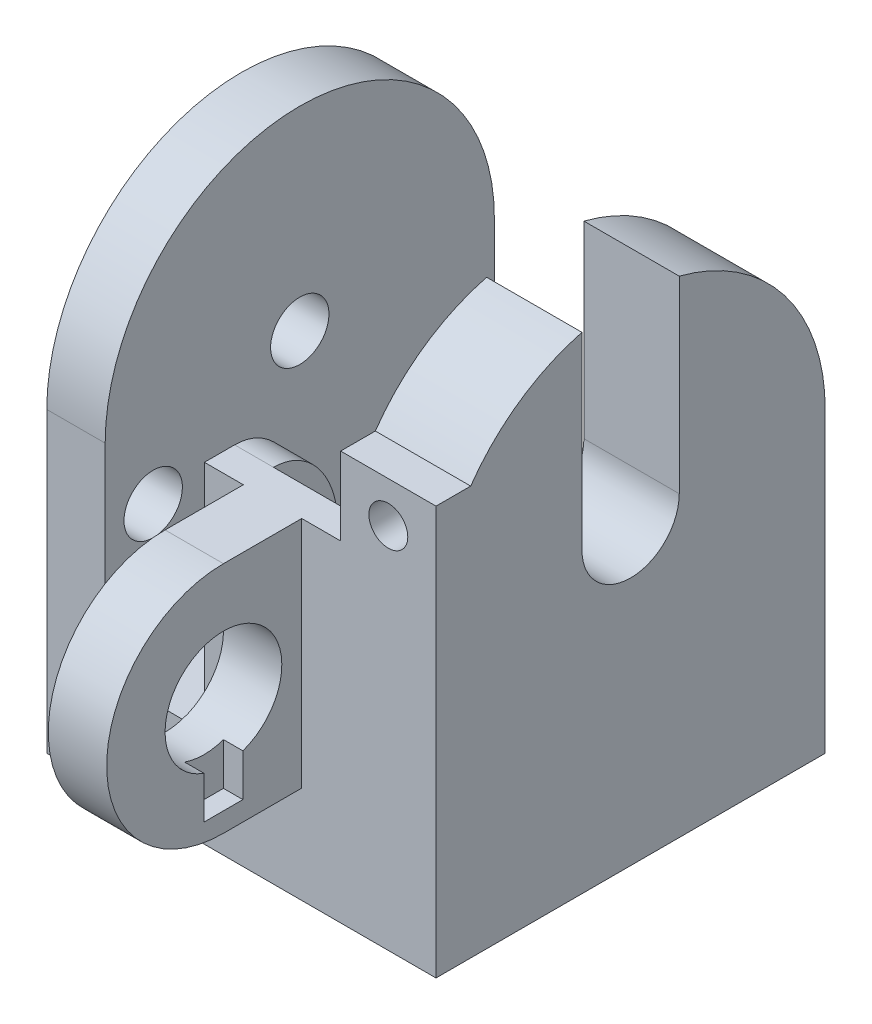
SolidWorks part; units mm, degrees
ref_plane "Front Plane" through (0, 0, 0) normal (0, 0, 1) x (1, 0, 0)
ref_plane "Top Plane" through (0, 0, 0) normal (0, 1, 0) x (1, 0, 0)
ref_plane "Right Plane" through (0, 0, 0) normal (1, 0, 0) x (0, 0, -1)
sketch "Sketch1" plane through (0, 0, 0) normal (1, 0, 0) x (0, 0, -1)
  arc A0 (9.7654, 20.1165) -> (-9.7654, 20.1165) centre (0, 22.2701) ccw
  arc A1 (-7.8874, -56.3924) -> (7.8874, -56.3924) centre (0, -57.7299) ccw
  arc A2 (-7.8874, -56.3924) -> (-9.7654, 20.1165) centre (-205.0724, -22.9549) ccw
  circle A3 centre (0, 22.2701) radius 1.5
  arc A4 (9.7654, 20.1165) -> (7.8874, -56.3924) centre (205.0724, -22.9549) ccw
  circle A5 centre (0, -57.7299) radius 2.5
extrude "Boss-Extrude1" add sketch "Sketch1" along normal blind 20
sketch "Sketch2" plane through (0, 0, 0) normal (0, 0, 1) x (1, 0, 0)
  line L1 (0, -65.7299) -> (8.1, -65.7299)
  line L2 (0, -65.7299) -> (0, -45.7299)
  line L3 (0, -45.7299) -> (8.1, -45.7299)
  line L4 (8.1, -65.7299) -> (8.1, -45.7299)
  line L5 (20, -65.7299) -> (14.9, -65.7299)
  line L6 (20, -65.7299) -> (20, -45.7299)
  line L7 (20, -45.7299) -> (14.9, -45.7299)
  line L8 (14.9, -65.7299) -> (14.9, -45.7299)
  line L11 (3, 32.2701) -> (8.1, 32.2701)
  line L12 (3, 32.2701) -> (3, 12.2701)
  line L13 (3, 12.2701) -> (8.1, 12.2701)
  line L14 (8.1, 32.2701) -> (8.1, 12.2701)
extrude "Cut-Extrude1" cut sketch "Sketch2" against normal blind 20 and the other way blind 20
sketch "Sketch3" plane through (8.1, 0, 0) normal (-1, 0, 0) x (0, 0, 1)
  line L0 (8.5, 22.2701) -> (8.5, 40.9095)
  line L1 (8.5, 40.9095) -> (-17.5287, 40.9095)
  line L2 (-17.5287, 40.9095) -> (-17.5287, 13.7701)
  line L3 (0, 13.7701) -> (-17.5287, 13.7701)
  arc A0 (0, 13.7701) -> (8.5, 22.2701) centre (0, 22.2701) ccw
extrude "Cut-Extrude2" cut sketch "Sketch3" against normal blind 9
sketch "Sketch4" plane through (8.1, 0, 0) normal (-1, 0, 0) x (0, 0, 1)
  line L0 (8.5, 27.5379) -> (8.2838, 12.7416)
  line L1 (8.2838, 12.7416) -> (10.2838, 12.7416)
  line L2 (10.2838, 12.7416) -> (10.2838, 27.5379)
  line L3 (10.2838, 27.5379) -> (8.5, 27.5379)
  arc A0 (9.7654, 20.1165) -> (6.3734, -45.7299) centre (205.0724, -22.9549) ccw construction
extrude "Boss-Extrude2" add sketch "Sketch4" against normal through all
sketch "Sketch5" plane through (8.1, 0, 0) normal (-1, 0, 0) x (0, 0, 1)
  line L4 (8.1452, 11.9686) -> (8.4478, 23.9686)
  line L6 (14.0224, 23.9686) -> (9.8547, 23.9686)
  line L8 (8.1452, 11.9686) -> (14.0224, 11.9686)
  line L9 (8.5, 27.5379) -> (8.4045, 20.9993) construction
  line L10 (8.4478, 23.9686) -> (9.8547, 23.9686)
  circle A2 centre (14.0224, 17.9686) radius 3
  arc A5 (14.0224, 11.9686) -> (14.0224, 23.9686) centre (14.0224, 17.9686) ccw
  arc A6 (9.7654, 20.1165) -> (-9.7654, 20.1165) centre (0, 22.2701) ccw construction
  arc A7 (9.7654, 20.1165) -> (6.3734, -45.7299) centre (205.0724, -22.9549) ccw construction
extrude "Boss-Extrude3" add sketch "Sketch5" against normal blind 5
sketch "Sketch12" plane through (13.1, 0, 0) normal (1, 0, 0) x (0, 0, -1)
  line L3 (-15.0224, 13.9686) -> (-15.0224, 12.9686)
  line L4 (-14.0224, 15.1402) -> (-15.0224, 15.1402)
  line L5 (-15.0224, 13.9686) -> (-15.0224, 15.1402)
  line L7 (-15.0224, 12.9686) -> (-13.0224, 12.9686)
  line L8 (-14.0224, 15.1402) -> (-13.0224, 15.1402)
  line L9 (-13.0224, 13.9686) -> (-13.0224, 15.1402)
  line L10 (-13.0224, 13.9686) -> (-13.0224, 12.9686)
  circle A0 centre (-14.0224, 17.9686) radius 3 construction
extrude "Cut-Extrude6" cut sketch "Sketch12" against normal blind 1
sketch "Sketch13" plane through (17.1, 0, 0) normal (-1, 0, 0) x (0, 0, 1)
  circle A0 centre (0, 22.2701) radius 2.5
extrude "Cut-Extrude7" cut sketch "Sketch13" against normal blind 4
sketch "Sketch15" plane through (0, 0, 0) normal (-1, 0, 0) x (0, 0, 1)
  line L0 (10, 22.2701) -> (10, 11.9686)
  line L1 (8.1452, 11.9686) -> (14.0224, 11.9686) construction
  line L2 (10, 11.9686) -> (8.1452, 11.9686)
  line L3 (10, 22.2701) -> (7.5957, 11.9686)
  line L4 (7.5957, 11.9686) -> (8.1452, 11.9686)
  arc A0 (9.7654, 20.1165) -> (-9.7654, 20.1165) centre (0, 22.2701) ccw construction
extrude "Boss-Extrude4" add sketch "Sketch15" against normal blind 3
sketch "Sketch16" plane through (20, 0, 0) normal (1, 0, 0) x (0, 0, -1)
  line L0 (-10.2838, 23.9686) -> (-9.8547, 23.9686)
  line L1 (-10.2838, 23.9686) -> (-10.2838, 27.5379)
  line L2 (-10.2838, 27.5379) -> (-8.5, 27.5379) construction
  line L3 (-10.2838, 12.7416) -> (-10.2838, 27.5379) construction
  line L4 (-10.2838, 27.5379) -> (-8.5, 27.5379)
  arc A0 (-8.5, 27.5379) -> (-9.8547, 23.9686) centre (0, 22.2701) ccw
extrude "Cut-Extrude9" cut sketch "Sketch16" against normal blind 3
sketch "Sketch17" plane through (0, 0, 10.2838) normal (0, 0, 1) x (1, 0, 0)
  line L1 (17.1, 27.5379) -> (8.1, 27.5379)
  line L2 (17.1, 27.5379) -> (17.1, 23.9686)
  line L3 (17.1, 23.9686) -> (8.1, 23.9686)
  line L4 (8.1, 27.5379) -> (8.1, 23.9686)
extrude "Cut-Extrude11" cut sketch "Sketch17" against normal blind 3
sketch "Sketch18" plane through (13.1, 0, 0) normal (1, 0, 0) x (0, 0, -1)
  line L1 (-10.2838, 12.7416) -> (-4.5128, 12.7416)
  line L2 (-10.2838, 12.7416) -> (-10.2838, 11.9686)
  line L3 (-10.2838, 11.9686) -> (-4.5128, 11.9686)
  line L4 (-4.5128, 12.7416) -> (-4.5128, 11.9686)
extrude "Boss-Extrude5" add sketch "Sketch18" along normal through all and the other way blind 1
sketch "Sketch19" plane through (0, 12.2701, 0) normal (0, 1, 0) x (1, 0, 0)
  line L1 (8.1, -8.1989) -> (3, -8.1989)
  line L2 (8.1, -8.1989) -> (8.1, 8.1989)
  line L3 (8.1, 8.1989) -> (3, 8.1989)
  line L4 (3, -8.1989) -> (3, 8.1989)
extrude "Cut-Extrude12" cut sketch "Sketch19" against normal up to surface (0.3015 mm away) up to face at (1.5, 11.9686, 9.0726)
sketch "Sketch20" plane through (17.1, 0, 0) normal (-1, 0, 0) x (0, 0, 1)
  line L1 (2.5, 22.2701) -> (-2.5, 22.2701)
  line L2 (2.5, 22.2701) -> (2.5, 34.6894)
  line L3 (2.5, 34.6894) -> (-2.5, 34.6894)
  line L4 (-2.5, 22.2701) -> (-2.5, 34.6894)
  circle A0 centre (0, 22.2701) radius 2.5 construction
extrude "Cut-Extrude13" cut sketch "Sketch20" against normal blind 10
sketch "Sketch21" plane through (17.1, 0, 0) normal (-1, 0, 0) x (0, 0, 1)
  line L1 (-8.4732, 13.7701) -> (0.2785, 12.274)
  line L3 (2.5, 22.2701) -> (2.5, 31.9526)
  line L5 (-2.5, 22.2701) -> (-2.5, 31.9526)
  arc A0 (0.2785, 12.274) -> (2.5, 31.9526) centre (0, 22.2701) ccw
  arc A1 (-2.5, 22.2701) -> (2.5, 22.2701) centre (0, 22.2701) ccw
  arc A2 (-2.5, 31.9526) -> (-9.7654, 20.1165) centre (0, 22.2701) ccw
  arc A7 (-8.4732, 13.7701) -> (-9.7654, 20.1165) centre (-205.0724, -22.9549) ccw
extrude "Boss-Extrude6" add sketch "Sketch21" along normal blind 2
sketch "Sketch23" plane through (0, 0, 10.2838) normal (0, 0, 1) x (1, 0, 0)
  line L1 (15.1, 23.9686) -> (20, 23.9686)
  line L2 (15.1, 23.9686) -> (15.1, 27.9686)
  line L3 (15.1, 27.9686) -> (20, 27.9686)
  line L4 (20, 23.9686) -> (20, 27.9686)
extrude "Boss-Extrude7" add sketch "Sketch23" against normal blind 4
sketch "Sketch22" plane through (0, 0, 10.2838) normal (0, 0, 1) x (1, 0, 0)
  circle A0 centre (17.55, 25.8701) radius 1
extrude "Cut-Extrude15" cut sketch "Sketch22" against normal blind 8
sketch "Sketch24" plane through (8.1, 0, 0) normal (-1, 0, 0) x (0, 0, 1)
  line L0 (5.1478, 19.7374) -> (5.1478, 15.5063)
  line L2 (8.4478, 23.9686) -> (8.4478, 15.5063)
  line L3 (8.4478, 15.5063) -> (5.1478, 15.5063)
  arc A0 (0, 13.7701) -> (8.3673, 20.7738) centre (0, 22.2701) ccw construction
  ellipse E0 centre (8.4478, 19.7374) end of major axis (8.4478, 15.5063) minor radius 3.3 (8.4478, 23.9686) -> (5.1478, 19.7374) ccw
extrude "Boss-Extrude8" add sketch "Sketch24" against normal blind 2
sketch "Sketch14" plane through (0, 0, 0) normal (-1, 0, 0) x (0, 0, 1)
  circle A3 centre (7.5326, 18.3318) radius 1.5
extrude "Cut-Extrude8" cut sketch "Sketch14" against normal up to surface (10.1 mm away) up to face at (10.1, 20.14, 6.7306)
sketch "Sketch25" plane through (8.1, 0, 0) normal (-1, 0, 0) x (0, 0, 1)
  line L0 (12, -45.7299) -> (8.3462, -36.9607)
  line L1 (-12, -45.7299) -> (-12, -57.7299)
  line L2 (12, -45.7299) -> (12, -57.7299)
  line L3 (-12, -45.7299) -> (-8.3462, -36.9607)
  line L5 (2.5, -53.2274) -> (2.5, -45.7299)
  line L7 (-2.5, -53.2274) -> (-2.5, -45.7299)
  arc A0 (-2.5, -53.2274) -> (2.5, -53.2274) centre (0, -57.7299) ccw
  arc A1 (-12, -57.7299) -> (12, -57.7299) centre (0, -57.7299) ccw
  arc A2 (2.5, -45.7299) -> (8.3462, -36.9607) centre (0, -37.7299) ccw
  arc A4 (-8.3462, -36.9607) -> (-2.5, -45.7299) centre (0, -37.7299) ccw
extrude "Cut-Extrude17" cut sketch "Sketch25" against normal blind 2 and the other way up to surface (8.1 mm away) other way up to face at (0, 18.3318, 9.0326)
sketch "Sketch29" plane through (20, 0, 0) normal (1, 0, 0) x (0, 0, -1)
  line L1 (8, -37.7299) -> (8.1403, -37.7299)
  line L2 (-15.7549, -37.7299) -> (-8, -37.7299)
  line L3 (-15.7549, -37.7299) -> (-15.7549, -45.9375)
  line L4 (-15.7549, -45.9375) -> (8.1403, -45.9375)
  line L5 (8.1403, -37.7299) -> (8.1403, -45.9375)
  arc A0 (-8, -37.7299) -> (8, -37.7299) centre (0, -37.7299) ccw
extrude "Cut-Extrude20" cut sketch "Sketch29" against normal up to surface (5.1 mm away) up to face at (14.9, -57.7299, -2.5)
sketch "Sketch31" plane through (0, 0, 0) normal (-1, 0, 0) x (0, 0, 1)
  line L1 (10, 11.9686) -> (-10, 11.9686)
  line L2 (10, 11.9686) -> (10, 6.9686)
  line L3 (10, 6.9686) -> (-7.3236, 6.9686)
  line L6 (-10, 11.9686) -> (-10, 6.9686)
  line L7 (-10, 6.9686) -> (-7.3236, 6.9686)
  arc A0 (-6.1254, -43.4508) -> (-9.7654, 20.1165) centre (-205.0724, -22.9549) ccw construction
extrude "Boss-Extrude9" add sketch "Sketch31" against normal through all
sketch "Sketch32" plane through (0, 0, 0) normal (-1, 0, 0) x (0, 0, 1)
  line L0 (7.3236, 6.9686) -> (10, 6.9686) construction
  line L1 (10, 6.9686) -> (-10, 6.9686)
  line L2 (10, 6.9686) -> (10, -74.1141)
  line L3 (10, -74.1141) -> (-10, -74.1141)
  line L4 (-10, 6.9686) -> (-10, -74.1141)
  line L5 (10, 6.9686) -> (10, 22.2701) construction
extrude "Cut-Extrude23" cut sketch "Sketch32" against normal through all
sketch "Sketch33" plane through (0, 0, -10) normal (0, 0, -1) x (-1, 0, 0)
  line L0 (-15.1, 13.7701) -> (-8.1, 13.7701) construction
  line L1 (-20, 11.9686) -> (-15.1, 11.9686)
  line L2 (-20, 11.9686) -> (-20, 20.1165)
  line L3 (-20, 22.2701) -> (-15.1, 22.2701)
  line L4 (-15.1, 13.7701) -> (-15.1, 20.1165)
  line L5 (-15.1, 11.9686) -> (-8.1, 11.9686)
  line L6 (-15.1, 22.2701) -> (-15.1, 20.1165)
  line L7 (-15.1, 13.7701) -> (-8.1, 13.7701)
  line L8 (-8.1, 11.9686) -> (-8.1, 13.7701)
  line L9 (-8.1, 13.7701) -> (-15.1, 13.7701) construction
  line L10 (-3, 22.2701) -> (-3, 20.1165)
  line L11 (-3, 11.9686) -> (0, 11.9686)
  line L12 (-3, 11.9686) -> (-3, 20.1165)
  line L13 (-20, 20.1165) -> (-20, 22.2701)
  line L14 (0, 11.9686) -> (0, 20.1165)
  line L15 (-3, 22.2701) -> (0, 22.2701)
  line L16 (0, 20.7701) -> (0, 23.7701) construction
  line L18 (0, 22.2701) -> (0, 20.1165)
extrude "Boss-Extrude10" add sketch "Sketch33" against normal blind 5
sketch "Sketch34" plane through (0, 0, 10.2838) normal (0, 0, 1) x (1, 0, 0)
  line L1 (13.1, 11.9686) -> (20, 11.9686)
  line L2 (13.1, 11.9686) -> (13.1, 34.4183)
  line L3 (13.1, 34.4183) -> (20, 34.4183)
  line L4 (20, 11.9686) -> (20, 34.4183)
extrude "Cut-Extrude24" cut sketch "Sketch34" against normal up to surface (0.2838 mm away) up to face at (7.7286, 13.4833, 10)
sketch "Sketch35" plane through (0, 23.9686, 0) normal (0, 1, 0) x (1, 0, 0)
  line L0 (8.1, -20.0224) -> (13.1, -20.0224) construction
  line L1 (8.1, -10) -> (10.1, -10)
  line L2 (8.1, -10) -> (8.1, -20.0224)
  line L3 (8.1, -20.0224) -> (10.1, -20.0224)
  line L4 (10.1, -10) -> (10.1, -20.0224)
extrude "Cut-Extrude25" cut sketch "Sketch35" against normal up to next
